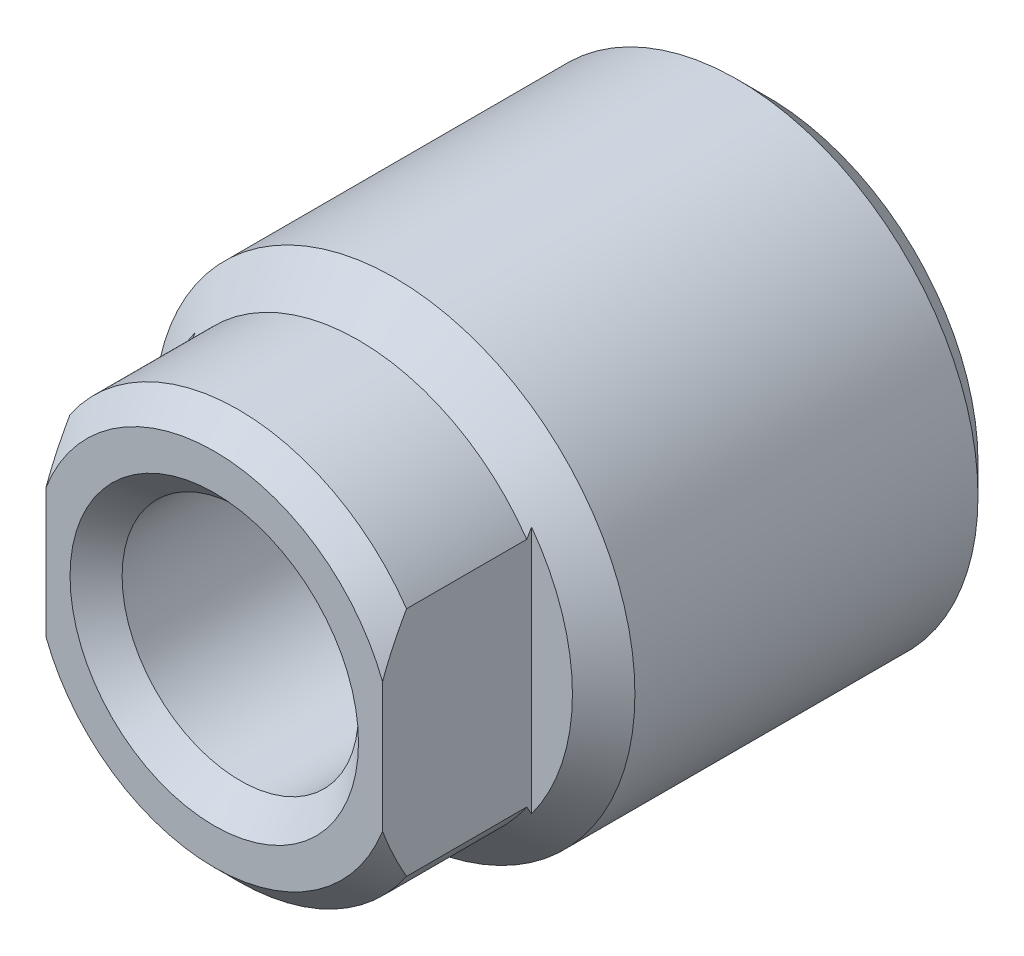
SolidWorks part; units mm, degrees
ref_plane "Ebene vorne" through (0, 0, 0) normal (0, 0, 1) x (1, 0, 0)
ref_plane "Ebene oben" through (0, 0, 0) normal (0, 1, 0) x (1, 0, 0)
ref_plane "Ebene rechts" through (0, 0, 0) normal (1, 0, 0) x (0, 0, -1)
sketch "Skizze1" plane through (0, 0, 0) normal (1, 0, 0) x (0, 0, -1)
  line L0 (-11.5, 3.75) -> (-11.5, 3)
  line L1 (-11.5, 3) -> (-10.9585, 2.4585)
  line L2 (-10.9585, 2.4585) -> (-0.5415, 2.4585)
  line L3 (-0.5415, 2.4585) -> (0, 3)
  line L4 (0, 3) -> (0, 4.3865)
  line L5 (0, 4.3865) -> (-0.6135, 5)
  line L6 (-0.6135, 5) -> (-7.75, 5)
  line L7 (-7.75, 5) -> (-8.5, 4.25)
  line L8 (-8.5, 4.25) -> (-11, 4.25)
  line L9 (-11, 4.25) -> (-11.5, 3.75)
  line L10 (0, 0) -> (-11.5, 0) construction
revolve "Rotation1" add sketch "Skizze1" angle 360 about L10 reverse direction yes
cosmetic thread "Gewindedarstellung1" parameters "D1"=8.3635, "D2"=8.773
cosmetic thread "Gewindedarstellung2" parameters "D1"=11.5, "D2"=6
sketch "Skizze2" plane through (0, 0, 0) normal (0, 1, 0) x (1, 0, 0)
  line L0 (-13.5, -23.4) -> (13.5, -23.4)
  line L1 (13.5, -23.4) -> (13.5, -8.4)
  line L2 (13.5, -8.4) -> (3.5, -8.4)
  line L3 (3.5, -8.4) -> (3.5, -18.4)
  line L4 (3.5, -18.4) -> (-3.5, -18.4)
  line L5 (-3.5, -18.4) -> (-3.5, -8.4)
  line L6 (-3.5, -8.4) -> (-13.5, -8.4)
  line L7 (-13.5, -8.4) -> (-13.5, -23.4)
extrude "Schnitt-Linear austragen1" cut sketch "Skizze2" along normal blind 30 and the other way blind 30
ref_plane "Ebene1" through (0, 0, 11.5) normal (0, 0, 1) x (1, 0, 0)
ref_plane "Ebene2" through (0, 0, 0) normal (1, 0, 0) x (0, 0, -1)
ref_plane "Ebene3" through (0, 0, 14.7) normal (0, 0, 1) x (1, 0, 0)
ref_plane "buchse XY" through (0, 0, 11.5) normal (0, 0, 1) x (1, 0, 0)
ref_plane "buchse XZ" through (0, 0, 0) normal (0, -1, 0) x (-1, 0, 0)
ref_plane "buchse YZ" through (0, 0, 0) normal (1, 0, 0) x (0, 0, -1)
ref_axis "buchse X" through (-80.9, 0, 11.5) along (1, 0, 0)
ref_axis "buchse Y" through (0, -50, 11.5) along (0, 1, 0)
ref_axis "buchse Z" through (0, 0, 80.9) along (0, 0, -1)
sketch3d "buchse"
  point P0 (0, 0, 11.5)
